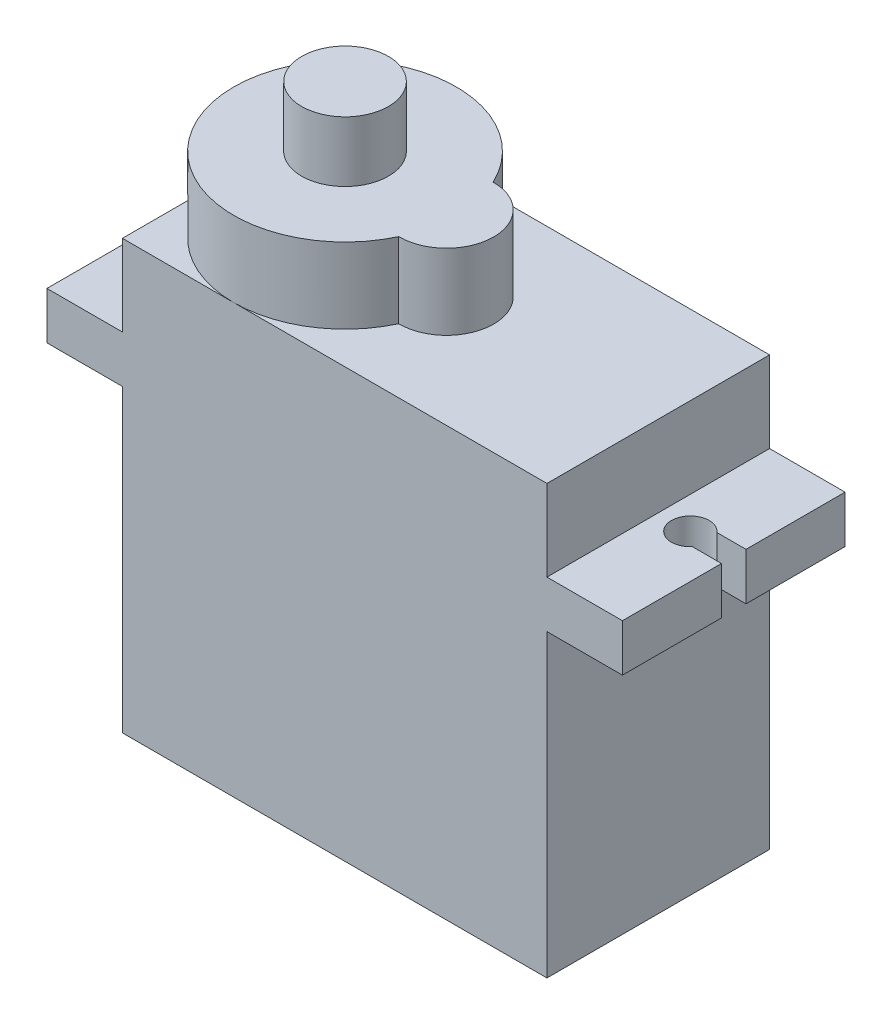
SolidWorks part; units mm, degrees
ref_plane "Front Plane" through (0, 0, 0) normal (0, 0, 1) x (1, 0, 0)
ref_plane "Top Plane" through (0, 0, 0) normal (0, 1, 0) x (1, 0, 0)
ref_plane "Right Plane" through (0, 0, 0) normal (1, 0, 0) x (0, 0, -1)
sketch "Sketch2" plane through (0, 0, 0) normal (0, 0, 1) x (1, 0, 0)
  line L1 (-5.9327, 14.8686) -> (16.5673, 14.8686)
  line L2 (-5.9327, 14.8686) -> (-5.9327, -7.8314)
  line L3 (-5.9327, -7.8314) -> (16.5673, -7.8314)
  line L4 (16.5673, 14.8686) -> (16.5673, -7.8314)
extrude "Boss-Extrude1" add sketch "Sketch2" along normal blind 11.8
sketch "Sketch3" plane through (0, 14.8686, 0) normal (0, 1, 0) x (1, 0, 0)
  circle A1 centre (-0.0327, -5.9) radius 5.9
  arc A3 (5.3116, -3.4002) -> (5.3116, -8.3998) centre (5.3441, -5.9) cw
extrude "Boss-Extrude2" add sketch "Sketch3" along normal blind 4 contours A1 | A3 A1 region at (-0.0327, 14.8686, 5.9) region at (6.5843, 14.8686, 5.9)
sketch "Sketch4" plane through (0, 18.8686, 0) normal (0, 1, 0) x (1, 0, 0)
  line L0 (-0.0327, 0) -> (-0.0327, -11.8)
  arc A0 (5.3116, -3.4002) -> (5.3116, -8.3998) centre (-0.0327, -5.9) ccw construction
  circle A1 centre (-0.0327, -5.9) radius 2.3
extrude "Boss-Extrude3" add sketch "Sketch4" along normal blind 3.2 contours A1
sketch "Sketch5" plane through (16.5673, 0, 0) normal (1, 0, 0) x (0, 0, -1)
  line L0 (0, -7.8314) -> (0, 14.8686) construction
  line L2 (-11.8, 10.5686) -> (-11.8, 8.0686)
  line L3 (-11.8, 10.5686) -> (0, 10.5686)
  line L4 (-11.8, 8.0686) -> (0, 8.0686)
  line L5 (0, 10.5686) -> (0, 8.0686)
  line L6 (-11.8, 10.5686) -> (0, 8.0686) construction
  line L7 (-11.8, 8.0686) -> (0, 10.5686) construction
  point P5 (-5.9, 9.3186)
extrude "Boss-Extrude4" add sketch "Sketch5" along normal blind 4 and the other way blind 26.5
sketch "Sketch7" plane through (0, 10.5686, 0) normal (0, 1, 0) x (1, 0, 0)
  line L0 (20.5673, -5.25) -> (20.5673, -6.55)
  line L1 (20.5673, 0) -> (20.5673, -11.8) construction
  line L2 (-9.9327, -4.9) -> (-9.9327, -6.2)
  line L3 (19.0272, -5.25) -> (20.5673, -5.25)
  line L4 (19.0272, -6.55) -> (20.5673, -6.55)
  line L6 (-8.3926, -4.9) -> (-9.9327, -4.9)
  line L7 (-8.3926, -6.2) -> (-9.9327, -6.2)
  arc A3 (-8.3926, -4.9) -> (-8.3926, -6.2) centre (-7.6327, -5.55) cw
  arc A4 (19.0272, -5.25) -> (19.0272, -6.55) centre (18.2673, -5.9) ccw
  point P8 (18.2673, -5.9)
  point P24 (-7.6327, -5.55)
  line M3 (20.5673, -11.8) -> (20.5673, 0)
extrude "Cut-Extrude1" cut sketch "Sketch7" against normal up to next contours L3 A4 L4 M3 | A3 L7 L2 L6 region at (18.8515, 10.5686, 5.9)
